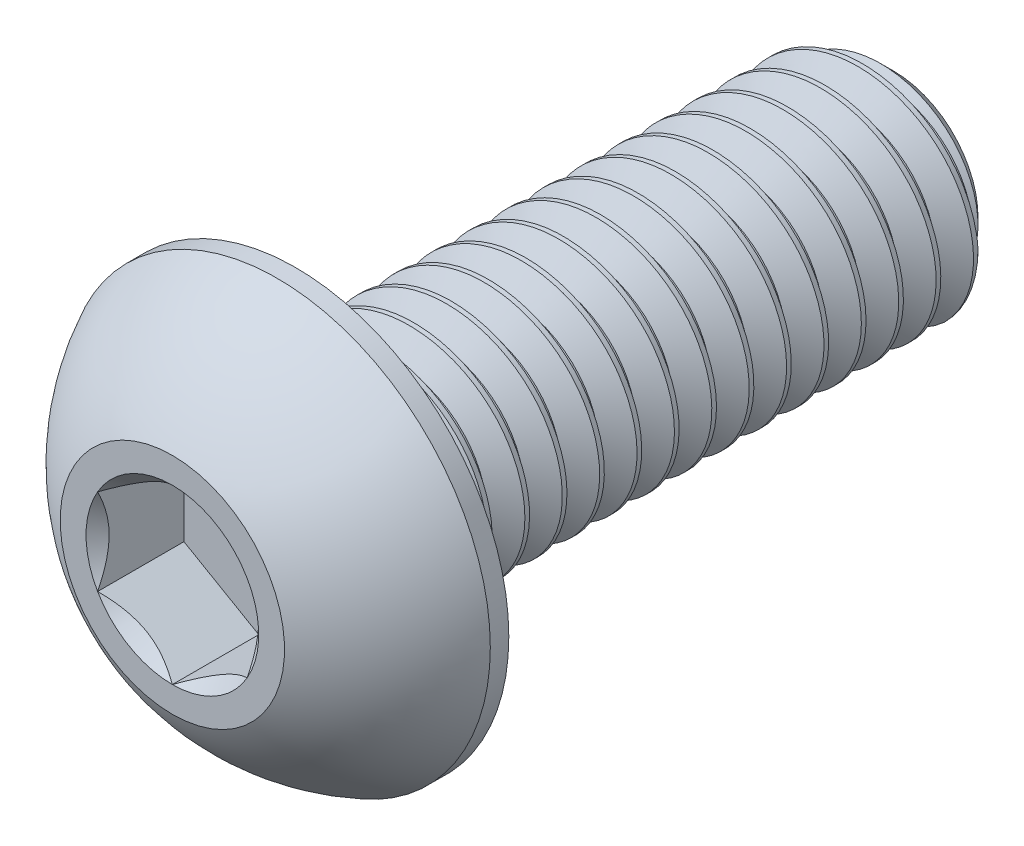
SolidWorks part; units mm, degrees
ref_plane "Front" through (0, 0, 0) normal (0, 0, 1) x (1, 0, 0)
ref_plane "Top" through (0, 0, 0) normal (0, 1, 0) x (1, 0, 0)
ref_plane "Right" through (0, 0, 0) normal (1, 0, 0) x (0, 0, -1)
sketch "Sketch1" plane through (0, 0, 0) normal (1, 0, 0) x (0, 0, -1)
  line L2 (1.65, 1.5) -> (9.65, 1.5)
  line L3 (9.65, 1.5) -> (9.65, 0)
  line L4 (9.65, 0) -> (1.65, 0)
  line L6 (1.4025, 2.85) -> (1.65, 2.85) construction
  line L7 (9.65, 1.5) -> (9.65, -1.5) construction
  line L8 (0, 0) -> (1.65, 0) construction
  line L9 (1.65, 2.85) -> (1.65, -2.85) construction
  line L11 (1.65, 1.5) -> (1.65, 0)
  line L13 (0, 1) -> (0, -1) construction
  line L14 (0, 1) -> (0, 1.5) construction
  arc A3 (0, 1.5) -> (1.4025, 2.85) centre (2.7948, 0) cw construction
  dimension "D1" = 0.2475
  dimension "Head Ht" = 1.65
  dimension "Head Dia" = 5.7
  dimension "Dia" = 3
  dimension "Lg" = 8
  dimension "Hex" = 2
revolve "Revolve1" add sketch "Sketch1" angle 360 mid plane about L4
sketch "Sketch3" plane through (0, 0, -9.65) normal (0, 0, -1) x (-1, 0, 0)
  circle A0 centre (0, 0) radius 1.5
curve "Helix/Spiral1" pitch 0.5 height 8.5 radius 1.5 centre (0, 0, -9.65) axis (0, 0, 1) start towards (0, 1, 0)
sketch "Sketch2" plane through (0, 0, 0) normal (1, 0, 0) x (0, 0, -1)
  line L0 (9.65, 1.5) -> (10.0875, 1.5)
  line L1 (10.0875, 1.5) -> (9.9, 1.1752)
  line L2 (9.9, 1.1752) -> (9.8375, 1.1752)
  line L3 (9.8375, 1.1752) -> (9.65, 1.5)
  line L4 (9.7438, 1.3376) -> (9.9938, 1.3376) construction
  dimension "D1" = 60
  dimension "D2" = 0.0625
  dimension "D3" = 0.25
chamfer "Chamfer1" distance 0.375 angle 45 1 edges at (0, 1.5, -9.65)
sweep "Cut-Sweep1" cut profiles "Sketch2" path "Helix/Spiral1" align with end faces yes
sketch "Sketch7" plane through (0, 0, 0) normal (1, 0, 0) x (0, 0, -1)
  line L6 (1.4025, 2.85) -> (1.65, 2.85) construction
  line L8 (0, 0) -> (1.65, 0) construction
  line L11 (1.65, 2.85) -> (1.65, -2.85) construction
  line L12 (1.4025, 2.85) -> (1.65, 2.85)
  line L13 (0, 0) -> (1.65, 0)
  line L14 (0, 1) -> (0, -1) construction
  line L15 (1.65, 2.85) -> (1.65, 0)
  line L16 (0, 1.5) -> (0, 0)
  arc A2 (1.4025, 2.85) -> (0, 1.5) centre (2.7948, 0) ccw construction
  arc A3 (1.4025, 2.85) -> (0, 1.5) centre (2.7948, 0) ccw
revolve "Revolve2" add sketch "Sketch7" angle 360 mid plane about L13
sketch "Sketch5" plane through (0, 0, 0) normal (0, 0, 1) x (1, 0, 0)
  line L1 (1, -0.5774) -> (1, 0.5774)
  line L2 (1, 0.5774) -> (0, 1.1547)
  line L3 (0, 1.1547) -> (-1, 0.5774)
  line L4 (-1, 0.5774) -> (-1, -0.5774)
  line L5 (-1, -0.5774) -> (0, -1.1547)
  line L6 (0, -1.1547) -> (1, -0.5774)
  circle A0 centre (0, 0) radius 1 construction
extrude "Cut-Extrude2" cut sketch "Sketch5" against normal blind 1.155
sketch "Sketch6" plane through (0, 0, 0) normal (0, 0, 1) x (1, 0, 0)
  circle A0 centre (0, 0) radius 1.1547
extrude "Cut-Extrude3" cut sketch "Sketch6" against normal blind 1.155 draft 45
sketch "Sketch9" [suppressed] plane through (0, 0, -4.2164) normal (0, 0, 1) x (1, 0, 0)
  circle A2 centre (0, 0) radius 3.9687
extrude "Boss-Extrude2" [suppressed] add sketch "Sketch9" against normal offset from surface (9.525 mm away) 28.575 up to face at (0, 1.125, -9.65)
sketch "Sketch10" plane through (0, 0, 0) normal (1, 0, 0) x (0, 0, -1)
  line L0 (9.65, 1.5) -> (9.65, -1.5) construction
  point P0 (8.9, -1.5)
  dimension "D1" = 0.75
equation "\"D3@Helix/Spiral1\" = \"Lg@Sketch1\" + \"D4@Helix/Spiral1\""
equation "\"D2@Sketch2\" = \"D4@Helix/Spiral1\" * .125"
equation "\"D3@Sketch2\" = \"D4@Helix/Spiral1\" * .5"
equation "\"D1@Chamfer1\" = \"D4@Helix/Spiral1\" * .75"
equation "\"D1@Cut-Extrude2\" = \"Head Ht@Sketch1\" * .7"
equation "\"D1@Sketch1\" = \"Head Ht@Sketch1\" * .15"
equation "\"D1@Sketch10\" = \"D4@Helix/Spiral1\" * 1.5"
equation "\"D1@Cut-Extrude3\" = \"D1@Cut-Extrude2\""
